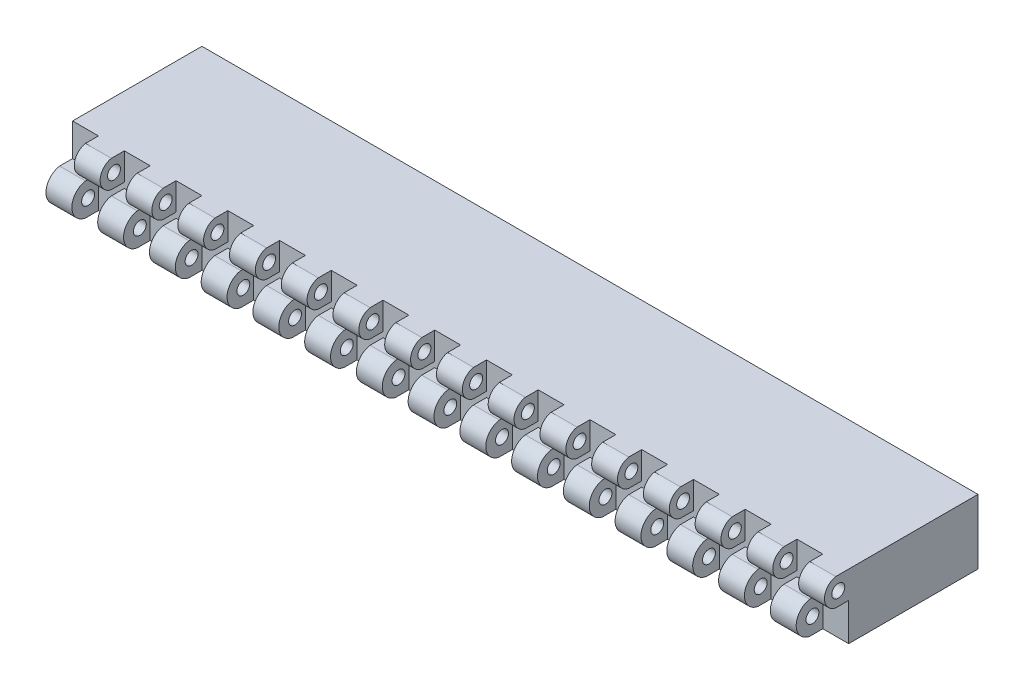
SolidWorks part; units mm, degrees
ref_plane "Front Plane" through (0, 0, 0) normal (0, 0, 1) x (1, 0, 0)
ref_plane "Top Plane" through (0, 0, 0) normal (0, 1, 0) x (1, 0, 0)
ref_plane "Right Plane" through (0, 0, 0) normal (1, 0, 0) x (0, 0, -1)
sketch "Sketch1" plane through (0, 0, 0) normal (1, 0, 0) x (0, 0, -1)
  line L1 (-25, 12.5) -> (25, 12.5)
  line L2 (-25, 12.5) -> (-25, -12.5)
  line L3 (-25, -12.5) -> (25, -12.5)
  line L4 (25, 12.5) -> (25, -12.5)
  line L5 (-25, 12.5) -> (25, -12.5) construction
  line L6 (-25, -12.5) -> (25, 12.5) construction
  point P0 (0, 0)
  dimension "D1" = 25
  dimension "D2" = 50
extrude "Boss-Extrude1" add sketch "Sketch1" along normal mid plane 300
sketch "Sketch2" plane through (150, 0, 0) normal (1, 0, 0) x (0, 0, -1)
  line L1 (-25, -12.5) -> (-25, 2) construction
  line L2 (-25, 2) -> (-25, 12.5)
  line L3 (-25, 2) -> (-30, 2)
  line L4 (-25, 12.5) -> (-30, 12.5)
  line L5 (25, 12.5) -> (-25, 12.5) construction
  arc A1 (-30, 12.5) -> (-30, 2) centre (-29, 7.25) ccw
  circle A2 centre (-29, 7.25) radius 2.5
  point P7 (-25, 7.25)
  dimension "D3" = 5
  dimension "D1" = 10.5
  dimension "D2" = 5
  dimension "D4" = 4
extrude "Boss-Extrude2" add sketch "Sketch2" against normal blind 10
pattern_linear "LPattern1" count 15 spacing 20 along (-1, 0, 0) of "Boss-Extrude2"
sketch "Sketch3" plane through (-150, 0, 0) normal (-1, 0, 0) x (0, 0, 1)
  line L0 (25, -12.5) -> (25, 0)
  line L1 (25, 12.5) -> (25, -12.5) construction
  line L2 (25, -12.5) -> (-25, -12.5) construction
  line L3 (25, -0.091) -> (30, -0.091)
  line L4 (25, -12.5) -> (30, -12.5)
  arc A1 (30, -12.5) -> (30, -0.091) centre (29, -6.2955) ccw
  circle A2 centre (29, -6.2955) radius 2.5
  point P7 (25, -6.25)
  dimension "D2" = 4
  dimension "D1" = 5
extrude "Boss-Extrude3" add sketch "Sketch3" against normal blind 10 contours L4 A1 L3 L0 A2 region at (-150, -6.2955, 25.1612)
pattern_linear "LPattern2" count 15 spacing 20 along (1, 0, 0) of "Boss-Extrude3"
sketch "Sketch4" plane through (0, 0, -25) normal (0, 0, -1) x (-1, 0, 0)
  circle A0 centre (0, 0) radius 7
  dimension "D1" = 14
extrude "Cut-Extrude1" cut sketch "Sketch4" against normal blind 30
